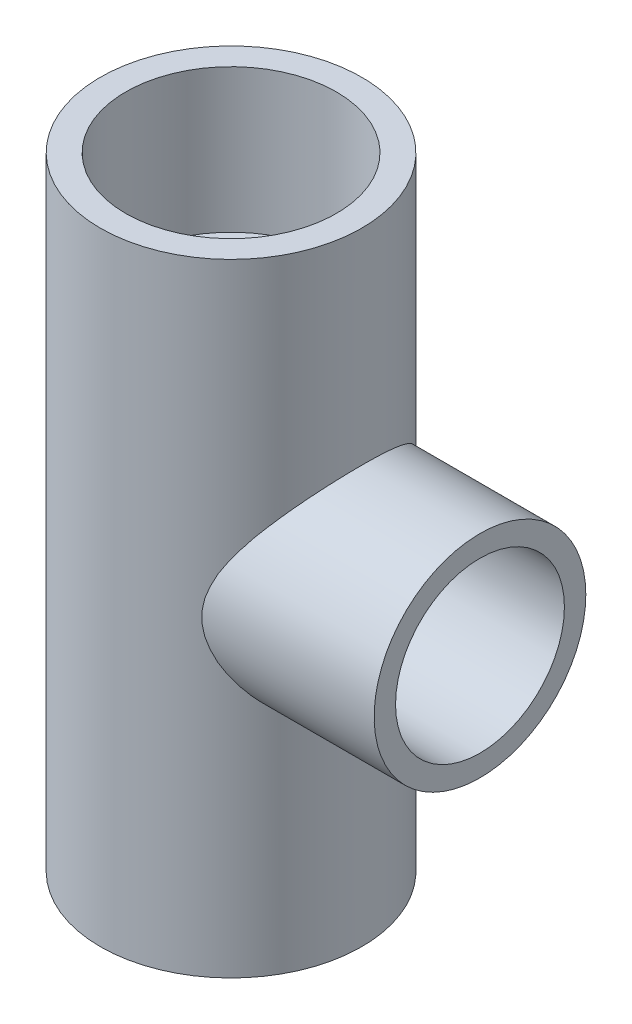
SolidWorks part; units mm, degrees
ref_plane "Front Plane" through (0, 0, 0) normal (0, 0, 1) x (1, 0, 0)
ref_plane "Top Plane" through (0, 0, 0) normal (0, 1, 0) x (1, 0, 0)
ref_plane "Right Plane" through (0, 0, 0) normal (1, 0, 0) x (0, 0, -1)
sketch "Sketch1" plane through (0, 0, 0) normal (0, 1, 0) x (1, 0, 0)
  circle A0 centre (0, 0) radius 16.6751
  circle A1 centre (0, 0) radius 10.4648
  dimension "D1" = 20.9296
  dimension "D2" = 33.3502
extrude "Boss-Extrude1" add sketch "Sketch1" along normal mid plane 79.375
sketch "Sketch2" plane through (0, 0, 0) normal (1, 0, 0) x (0, 0, -1)
  circle A0 centre (0, 0) radius 13.5001
  circle A1 centre (0, 0) radius 7.8994
  dimension "D1" = 27.0002
  dimension "D2" = 15.7988
ref_plane "Plane1" through (31.75, 0, 0) normal (1, 0, 0) x (0, 0, -1)
extrude "Boss-Extrude2" add sketch "Sketch2" along normal up to surface (31.75 mm away) separate body up to plane "Plane1"
sketch "Sketch4" plane through (31.75, 0, 0) normal (1, 0, 0) x (0, 0, -1)
  circle A0 centre (0, 0) radius 7.8994 construction
  circle A1 centre (0, 0) radius 7.8994
extrude "Cut-Extrude3" cut sketch "Sketch4" against normal up to surface (31.75 mm away) up to plane "Right Plane"
sketch "Sketch5" plane through (0, 39.6875, 0) normal (0, 1, 0) x (1, 0, 0)
  circle A0 centre (0, 0) radius 10.4648 construction
  circle A1 centre (0, 0) radius 10.4648
extrude "Cut-Extrude4" cut sketch "Sketch5" against normal up to surface (79.375 mm away) up to face at (0, -39.6875, 16.6751)
sketch "Sketch6" plane through (31.75, 0, 0) normal (1, 0, 0) x (0, 0, -1)
  circle A0 centre (0, 0) radius 13.5001 construction
  circle A1 centre (0, 0) radius 13.5001 construction
  circle A2 centre (0, 0) radius 10.7696
  dimension "D1" = 21.5392
extrude "Cut-Extrude5" cut sketch "Sketch6" against normal blind 17.526
sketch "Sketch8" plane through (0, 39.6875, 0) normal (0, 1, 0) x (1, 0, 0)
  circle A0 centre (0, 0) radius 13.4366
  dimension "D1" = 26.8732
extrude "Cut-Extrude6" cut sketch "Sketch8" against normal blind 18.288
mirror "Mirror1" about plane through (0, 0, 0) normal (0, 1, 0) of "Cut-Extrude6"
